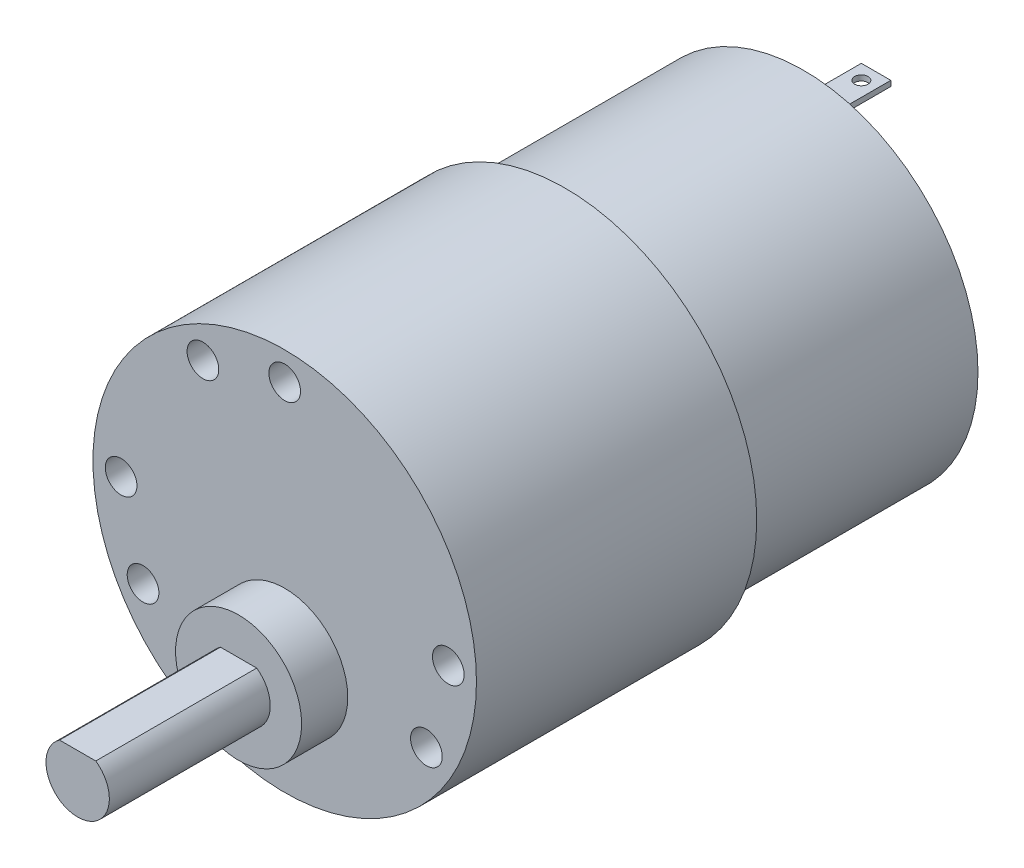
SolidWorks part; units mm, degrees
ref_plane "Front Plane" through (0, 0, 0) normal (0, 0, 1) x (1, 0, 0)
ref_plane "Top Plane" through (0, 0, 0) normal (0, 1, 0) x (1, 0, 0)
ref_plane "Right Plane" through (0, 0, 0) normal (1, 0, 0) x (0, 0, -1)
sketch "Sketch1" plane through (0, 0, 0) normal (0, 0, 1) x (1, 0, 0)
  circle A0 centre (0, 0) radius 18.161
  dimension "D1" = 36.322
extrude "Boss-Extrude1" add sketch "Sketch1" along normal blind 26.543
sketch "Sketch2" plane through (0, 0, 0) normal (0, 0, -1) x (-1, 0, 0)
  circle A0 centre (0, 0) radius 16.51
  dimension "D1" = 33.02
extrude "Boss-Extrude2" add sketch "Sketch2" along normal blind 22.606
sketch "Sketch3" plane through (0, 0, -22.606) normal (0, 0, -1) x (-1, 0, 0)
  circle A0 centre (0, 0) radius 4.5085
  dimension "D1" = 9.017
extrude "Boss-Extrude3" add sketch "Sketch3" along normal blind 3.302
sketch "Sketch4" plane through (0, 0, -22.606) normal (0, 0, -1) x (-1, 0, 0)
  circle A0 centre (0, -12.7) radius 2.413
  circle A1 centre (0, 12.7) radius 2.413
  circle A2 centre (0, 0) radius 18.161 construction
  dimension "D1" = 4.826
  dimension "D2" = 4.826
  dimension "D3" = 12.7
  dimension "D4" = 12.7
extrude "Boss-Extrude4" add sketch "Sketch4" along normal blind 1.27
sketch "Sketch5" plane through (0, 0, 26.543) normal (0, 0, 1) x (1, 0, 0)
  circle A0 centre (0, -7.366) radius 5.969
  dimension "D1" = 11.938
  dimension "D2" = 7.366
extrude "Boss-Extrude5" add sketch "Sketch5" along normal blind 4.3688
sketch "Sketch6" plane through (0, 0, 30.9118) normal (0, 0, 1) x (1, 0, 0)
  line L0 (-1.7157, -4.905) -> (1.7157, -4.905)
  arc A0 (-1.7157, -4.905) -> (1.7157, -4.905) centre (0, -7.366) ccw
  dimension "D1" = 6
  dimension "D2" = 2.461
extrude "Boss-Extrude6" add sketch "Sketch6" along normal blind 15.24
ref_axis "Axis2" through (0, 12.7, -23.876) along (0, 0, 1)
ref_axis "Axis3" through (0, -12.7, -23.876) along (0, 0, 1)
ref_plane "Plane1" through (0, 0, 0) normal (1, 0, 0) x (0, 0, -1)
ref_plane "Plane2" through (0, 12.7, 0) normal (0, 1, 0) x (0, 0, 1)
ref_plane "Plane3" through (0, -12.7, 0) normal (0, 1, 0) x (0, 0, 1)
sketch "Sketch8" plane through (0, 12.7, 0) normal (0, 1, 0) x (0, 0, 1)
  line L0 (-23.876, 2.413) -> (-23.876, -2.413) construction
  line L1 (-23.876, 1.397) -> (-29.464, 1.397)
  line L2 (-23.876, 1.397) -> (-23.876, -1.397)
  line L3 (-23.876, -1.397) -> (-29.464, -1.397)
  line L4 (-29.464, 1.397) -> (-29.464, -1.397)
  line L5 (0.6985, 0) -> (-0.6985, 0) construction
  circle A0 centre (-28.067, 0) radius 0.635
  dimension "D4" = 1.27
  dimension "D1" = 2.794
  dimension "D2" = 1.397
  dimension "D3" = 5.588
  dimension "D5" = 1.397
extrude "Boss-Extrude7" add sketch "Sketch8" along normal mid plane 0.508
pattern_circular "CirPattern1" count 2 over 360 about axis through (0, 0, -25.908) along (0, 0, 1) of "Boss-Extrude7"
sketch "Sketch9" plane through (0, 0, 26.543) normal (0, 0, 1) x (1, 0, 0)
  line L0 (0, 0) -> (0, 15.494) construction
  circle A0 centre (0, 0) radius 15.494 construction
  dimension "D1" = 30.988
hole_wizard "Ø3.0mm Dowel Hole1" positions "Sketch11" profile "Sketch12" hole size "Ø3.0" standard "ANSI Metric"
sketch "Sketch11" plane through (0, 0, 26.543) normal (0, 0, 1) x (1, 0, 0)
  point P0 (0, 15.494)
sketch "Sketch12" plane through (0, 15.494, 26.543) normal (1, 0, 0) x (0, -1, 0)
  line L0 (0, 0) -> (0, 11.0613)
  line L1 (0, 11.0613) -> (1.5, 10.16)
  line L2 (1.5, 10.16) -> (1.5, 0)
  line L5 (1.5, 0) -> (0, 0)
  line L10 (0, 11.0613) -> (-1.5, 10.16) construction
  line L11 (0, -6.35) -> (0, 107.95) construction
  dimension "Hole Dia." = 3
  dimension "Hole Depth" = 10.16
  dimension "Drill Angle" = 118
pattern_circular "CirPattern2" count 12 over 360 about axis through (0, 0, 26.543) along (0, 0, -1) skipping 1, 2, 5, 6, 10 of "Ø3.0mm Dowel Hole1"
